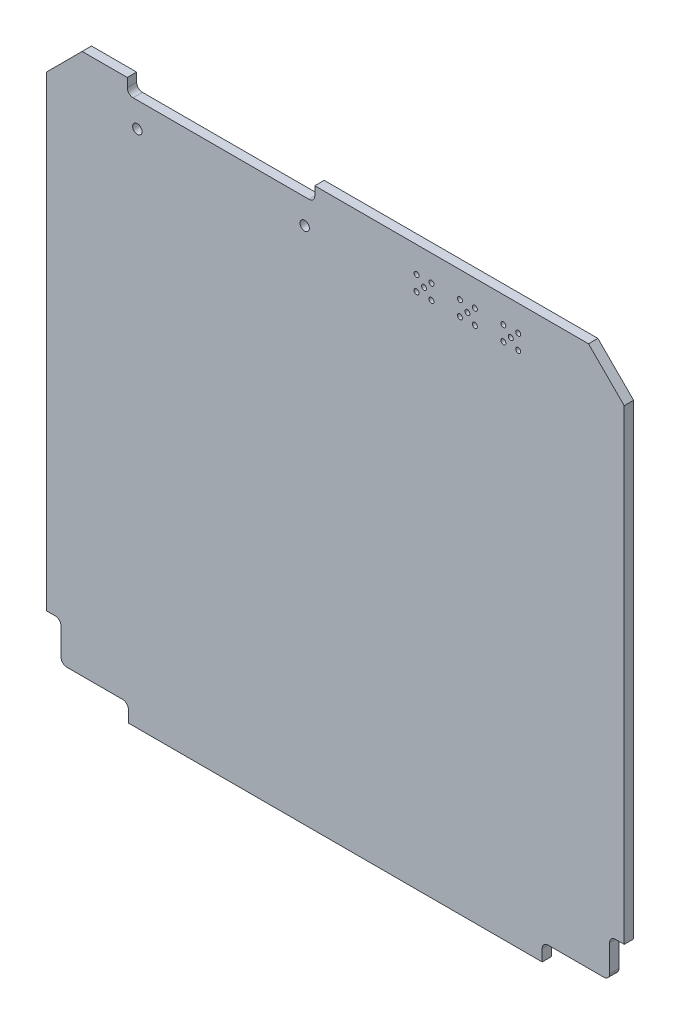
SolidWorks part; units mm, degrees
ref_plane "Front Plane" through (0, 0, 0) normal (0, 0, 1) x (1, 0, 0)
ref_plane "Top Plane" through (0, 0, 0) normal (0, 1, 0) x (1, 0, 0)
ref_plane "Right Plane" through (0, 0, 0) normal (1, 0, 0) x (0, 0, -1)
ref_plane "Plane4" through (0, 0, -0.0125) normal (0, 0, -1) x (-1, 0, 0)
sketch "Sketch1" plane through (0, 0, -0.0125) normal (0, 0, -1) x (-1, 0, 0)
  line L0 (35.3, -50) -> (35.3, -48)
  line L1 (36.3, -47) -> (45.8, -47)
  line L2 (46.8, -46) -> (46.8, -41.4)
  line L3 (47.8, -40.4) -> (49.3, -40.4)
  line L4 (49.3, -40.4) -> (49.3, 39.2)
  line L5 (49.3, 39.2) -> (43.2, 45.3)
  line L6 (43.2, 45.3) -> (35.5, 45.3)
  line L7 (35.5, 45.3) -> (35.5, 43.8)
  line L8 (34.5, 42.8) -> (4.5, 42.8)
  line L9 (3.5, 43.8) -> (3.5, 45.3)
  line L10 (3.5, 45.3) -> (-43.2, 45.3)
  line L11 (-43.2, 45.3) -> (-49.3, 39.2)
  line L12 (-49.3, 39.2) -> (-49.3, -40.4)
  line L13 (-49.3, -40.4) -> (-47.8, -40.4)
  line L14 (-46.8, -41.4) -> (-46.8, -46)
  line L15 (-45.8, -47) -> (-36.3, -47)
  line L16 (-35.3, -48) -> (-35.3, -50)
  line L17 (-35.3, -50) -> (35.3, -50)
  line L18 (0, -50) -> (0, 45.3) construction
  line L19 (19.5, 42.8) -> (19.5, 25.5258) construction
  line L20 (-13.87, 40.87) -> (-16.41, 38.33) construction
  line L21 (-21.27, 40.87) -> (-23.81, 38.33) construction
  line L22 (-28.67, 40.87) -> (-31.21, 38.33) construction
  arc A0 (35.3, -48) -> (36.3, -47) centre (36.3, -48) cw
  arc A1 (45.8, -47) -> (46.8, -46) centre (45.8, -46) ccw
  arc A2 (46.8, -41.4) -> (47.8, -40.4) centre (47.8, -41.4) cw
  arc A3 (35.5, 43.8) -> (34.5, 42.8) centre (34.5, 43.8) cw
  arc A4 (4.5, 42.8) -> (3.5, 43.8) centre (4.5, 43.8) cw
  arc A5 (-47.8, -40.4) -> (-46.8, -41.4) centre (-47.8, -41.4) cw
  arc A6 (-46.8, -46) -> (-45.8, -47) centre (-45.8, -46) ccw
  arc A7 (-36.3, -47) -> (-35.3, -48) centre (-36.3, -48) cw
  circle A8 centre (-21.27, 40.87) radius 0.425
  circle A9 centre (-23.81, 40.87) radius 0.425
  circle A10 centre (-22.54, 39.6) radius 0.425
  circle A11 centre (-13.87, 40.87) radius 0.425
  circle A12 centre (-23.81, 38.33) radius 0.425
  circle A13 centre (-16.41, 40.87) radius 0.425
  circle A14 centre (-15.14, 39.6) radius 0.425
  circle A15 centre (-21.27, 38.33) radius 0.425
  circle A16 centre (-28.67, 40.87) radius 0.425
  circle A17 centre (-31.21, 40.87) radius 0.425
  circle A18 centre (-16.41, 38.33) radius 0.425
  circle A19 centre (-29.94, 39.6) radius 0.425
  circle A20 centre (-31.21, 38.33) radius 0.425
  circle A21 centre (-28.67, 38.33) radius 0.425
  circle A22 centre (33.775, 38.54) radius 0.8
  circle A23 centre (5.225, 38.54) radius 0.8
  circle A24 centre (-13.87, 38.33) radius 0.425
  point P35 (-15.14, 39.6)
  point P37 (0, 0)
  point P75 (0, 0)
  point P76 (0, 0)
  point P77 (0, 0)
  point P78 (0, 0)
  point P79 (0, 0)
  point P80 (0, 0)
  dimension "D7" = 2.5
  dimension "D8" = 1.6
  dimension "D9" = 14.275
  dimension "D10" = 4.26
  dimension "D11" = 1
  dimension "D12" = 1
  dimension "D13" = 1
  dimension "D14" = 1
  dimension "D15" = 1
  dimension "D16" = 1
  dimension "D17" = 1
  dimension "D18" = 1
  dimension "D26" = 0.85
  dimension "D1" = 98.6
  dimension "D2" = 95.3
  dimension "D3" = 14
  dimension "D4" = 9.6
  dimension "D5" = 2.5
  dimension "D6" = 3
  dimension "D19" = 14
  dimension "D20" = 2.5
  dimension "D21" = 6.1
  dimension "D22" = 6.1
  dimension "D23" = 32
  dimension "D24" = 2.54
  dimension "D25" = 2.54
  dimension "D28" = 7.4
  dimension "D29" = 4.43
  dimension "D30" = 35.43
  dimension "D31" = 45
  dimension "D32" = 45
  dimension "D33" = 29.8
  dimension "D34" = 50
  dimension "D27" = 3
extrude "Boss-Extrude1" add sketch "Sketch1" against normal blind 1.6
